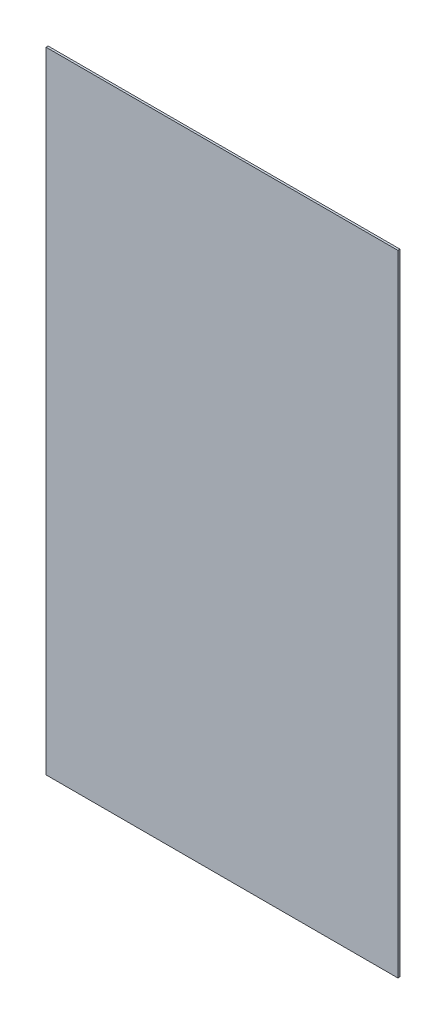
SolidWorks part; units mm, degrees
ref_plane "Front Plane" through (0, 0, 0) normal (0, 0, 1) x (1, 0, 0)
ref_plane "Top Plane" through (0, 0, 0) normal (0, 1, 0) x (1, 0, 0)
ref_plane "Right Plane" through (0, 0, 0) normal (1, 0, 0) x (0, 0, -1)
sketch "Sketch2" plane through (0, 0, 0) normal (0, 0, 1) x (1, 0, 0)
  line L1 (-265.4, 475.4) -> (265.4, 475.4)
  line L2 (-265.4, 475.4) -> (-265.4, -475.4)
  line L3 (-265.4, -475.4) -> (265.4, -475.4)
  line L4 (265.4, 475.4) -> (265.4, -475.4)
  line L5 (-265.4, 475.4) -> (265.4, -475.4) construction
  line L6 (-265.4, -475.4) -> (265.4, 475.4) construction
  point P0 (0, 0)
  dimension "Length 1" = 530.8
  dimension "Length 2" = 950.8
extrude "Boss-Extrude1" add sketch "Sketch2" along normal blind 3.175
